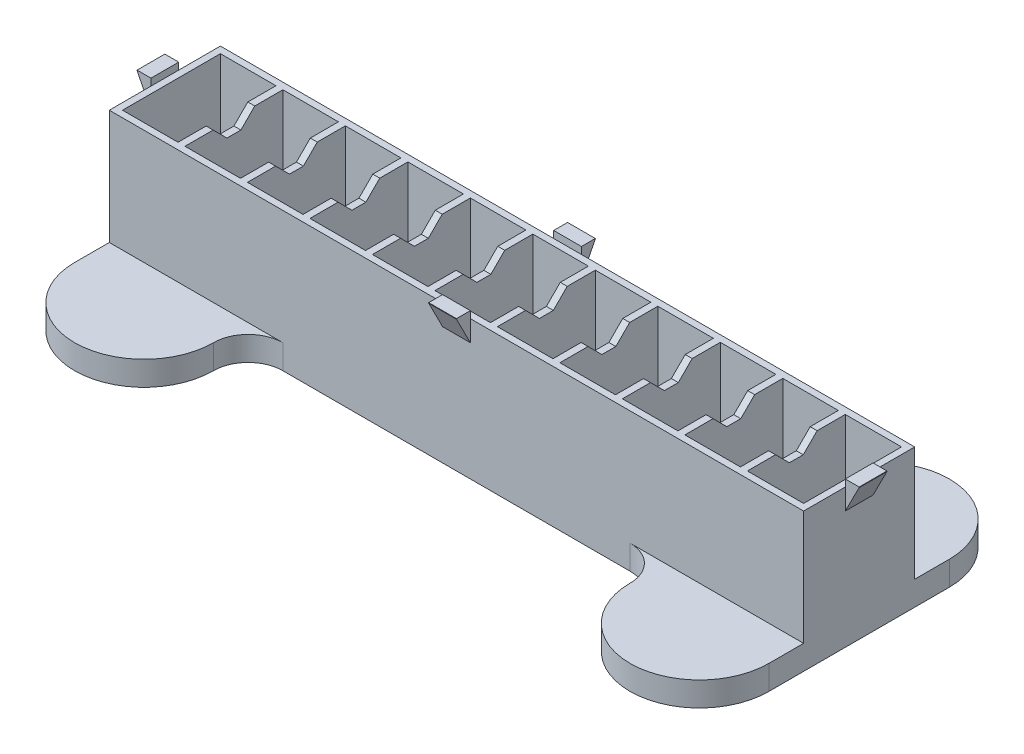
SolidWorks part; units mm, degrees
ref_plane "Front Plane" through (0, 0, 0) normal (0, 0, 1) x (1, 0, 0)
ref_plane "Top Plane" through (0, 0, 0) normal (0, 1, 0) x (1, 0, 0)
ref_plane "Right Plane" through (0, 0, 0) normal (1, 0, 0) x (0, 0, -1)
sketch "Sketch1" plane through (0, 0, 0) normal (0, 1, 0) x (1, 0, 0)
  line L1 (-275.0588, 111.5294) -> (-175.0588, 111.5294)
  line L2 (-275.0588, 111.5294) -> (-275.0588, 95.5294)
  line L3 (-275.0588, 95.5294) -> (-175.0588, 95.5294)
  line L4 (-175.0588, 111.5294) -> (-175.0588, 95.5294)
  dimension "D1" = 16
  dimension "D2" = 100
extrude "Boss-Extrude1" add sketch "Sketch1" along normal blind 20
sketch "Sketch2" plane through (-275.0588, 0, 0) normal (-1, 0, 0) x (0, 0, 1)
  line L0 (-111.5294, 20) -> (-95.5294, 20) construction
  line L1 (-110.5794, 20) -> (-96.4794, 20)
  line L2 (-110.5794, 20) -> (-110.5794, 8)
  line L4 (-96.4794, 20) -> (-96.4794, 8)
  line L5 (-111.5294, 20) -> (-111.5294, 0) construction
  arc A0 (-110.5794, 8) -> (-96.4794, 8) centre (-103.5294, 8) ccw
  point P8 (-103.5294, 20)
  point P9 (-103.5294, 20)
  dimension "D1" = 12
  dimension "D3" = 0.95
extrude "Cut-Extrude2" cut sketch "Sketch2" against normal blind 100
sketch "Sketch3" plane through (0, 20, 0) normal (0, 1, 0) x (1, 0, 0)
  line L0 (-225.0588, 111.5294) -> (-225.0588, 95.5294) construction
  line L1 (-175.0588, 111.5294) -> (-275.0588, 111.5294) construction
  line L2 (-275.0588, 95.5294) -> (-175.0588, 95.5294) construction
  line L3 (-175.0588, 95.5294) -> (-176.0088, 95.5294)
  line L4 (-275.0588, 111.5294) -> (-274.1088, 111.5294)
  line L5 (-275.0588, 111.5294) -> (-275.0588, 95.5294)
  line L6 (-275.0588, 95.5294) -> (-274.1088, 95.5294)
  line L7 (-274.1088, 111.5294) -> (-274.1088, 95.5294)
  line L8 (-175.0588, 111.5294) -> (-176.0088, 111.5294)
  line L9 (-176.0088, 111.5294) -> (-176.0088, 95.5294)
  line L10 (-175.0588, 111.5294) -> (-175.0588, 95.5294)
  dimension "D1" = 0.95
extrude "Boss-Extrude2" add sketch "Sketch3" against normal blind 20
sketch3d "3DSketch1" plane through (0, 0, 0) normal (0, 0, 1) x (1, 0, 0)
  dimension "D1" = 50
sketch "Sketch4" plane through (0, 20, 0) normal (0, 1, 0) x (1, 0, 0)
  line L0 (-274.1088, 103.5294) -> (-176.0088, 103.5294) construction
  line L1 (-274.1088, 96.4794) -> (-274.1088, 110.5794) construction
  line L2 (-176.0088, 110.5794) -> (-176.0088, 96.4794) construction
  line L3 (-176.0088, 110.5794) -> (-274.1088, 110.5794) construction
  line L4 (-266.1088, 110.5794) -> (-265.1088, 110.5794)
  line L5 (-266.1088, 110.5794) -> (-266.1088, 96.4794)
  line L6 (-266.1088, 96.4794) -> (-265.1088, 96.4794)
  line L7 (-265.1088, 110.5794) -> (-265.1088, 96.4794)
  line L8 (-176.0088, 96.4794) -> (-274.1088, 96.4794) construction
  line L9 (-265.1088, 103.5294) -> (-167.0088, 103.5294) construction
  line L10 (-257.1088, 110.5794) -> (-257.1088, 96.4794)
  line L11 (-256.1088, 110.5794) -> (-256.1088, 96.4794)
  line L12 (-257.1088, 96.4794) -> (-256.1088, 96.4794)
  line L13 (-257.1088, 110.5794) -> (-256.1088, 110.5794)
  line L14 (-256.1088, 103.5294) -> (-158.0088, 103.5294) construction
  line L15 (-248.1088, 110.5794) -> (-248.1088, 96.4794)
  line L16 (-247.1088, 110.5794) -> (-247.1088, 96.4794)
  line L17 (-248.1088, 96.4794) -> (-247.1088, 96.4794)
  line L18 (-248.1088, 110.5794) -> (-247.1088, 110.5794)
  line L19 (-247.1088, 103.5294) -> (-149.0088, 103.5294) construction
  line L20 (-239.1088, 110.5794) -> (-239.1088, 96.4794)
  line L21 (-238.1088, 110.5794) -> (-238.1088, 96.4794)
  line L22 (-239.1088, 96.4794) -> (-238.1088, 96.4794)
  line L23 (-239.1088, 110.5794) -> (-238.1088, 110.5794)
  line L24 (-238.1088, 103.5294) -> (-140.0088, 103.5294) construction
  line L25 (-230.1088, 110.5794) -> (-230.1088, 96.4794)
  line L26 (-229.1088, 110.5794) -> (-229.1088, 96.4794)
  line L27 (-230.1088, 96.4794) -> (-229.1088, 96.4794)
  line L28 (-230.1088, 110.5794) -> (-229.1088, 110.5794)
  line L29 (-229.1088, 103.5294) -> (-131.0088, 103.5294) construction
  line L30 (-221.1088, 110.5794) -> (-221.1088, 96.4794)
  line L31 (-220.1088, 110.5794) -> (-220.1088, 96.4794)
  line L32 (-221.1088, 96.4794) -> (-220.1088, 96.4794)
  line L33 (-221.1088, 110.5794) -> (-220.1088, 110.5794)
  line L34 (-220.1088, 103.5294) -> (-122.0088, 103.5294) construction
  line L35 (-212.1088, 110.5794) -> (-212.1088, 96.4794)
  line L36 (-211.1088, 110.5794) -> (-211.1088, 96.4794)
  line L37 (-212.1088, 96.4794) -> (-211.1088, 96.4794)
  line L38 (-212.1088, 110.5794) -> (-211.1088, 110.5794)
  line L39 (-211.1088, 103.5294) -> (-113.0088, 103.5294) construction
  line L40 (-203.1088, 110.5794) -> (-203.1088, 96.4794)
  line L41 (-202.1088, 110.5794) -> (-202.1088, 96.4794)
  line L42 (-203.1088, 96.4794) -> (-202.1088, 96.4794)
  line L43 (-203.1088, 110.5794) -> (-202.1088, 110.5794)
  line L44 (-202.1088, 103.5294) -> (-104.0088, 103.5294) construction
  line L45 (-194.1088, 110.5794) -> (-194.1088, 96.4794)
  line L46 (-193.1088, 110.5794) -> (-193.1088, 96.4794)
  line L47 (-194.1088, 96.4794) -> (-193.1088, 96.4794)
  line L48 (-194.1088, 110.5794) -> (-193.1088, 110.5794)
  line L49 (-193.1088, 103.5294) -> (-95.0088, 103.5294) construction
  line L50 (-185.1088, 110.5794) -> (-185.1088, 96.4794)
  line L51 (-184.1088, 110.5794) -> (-184.1088, 96.4794)
  line L52 (-185.1088, 96.4794) -> (-184.1088, 96.4794)
  line L53 (-185.1088, 110.5794) -> (-184.1088, 110.5794)
  line L54 (-176.0088, 110.5794) -> (-176.0088, 96.4794) construction
  dimension "D1" = 8
  dimension "D2" = 9
  dimension "D4" = 8.1
  dimension "D3" = 10
extrude "Boss-Extrude3" add sketch "Sketch4" against normal blind 20
sketch "Sketch5" plane through (0, 20, 0) normal (0, 1, 0) x (1, 0, 0)
  line L0 (-274.1088, 103.5294) -> (-176.0088, 103.5294) construction
  line L1 (-274.1088, 96.4794) -> (-274.1088, 110.5794) construction
  line L2 (-176.0088, 110.5794) -> (-176.0088, 96.4794) construction
  line L4 (-272.5588, 102.5294) -> (-177.5588, 102.5294)
  line L5 (-272.5588, 102.5294) -> (-272.5588, 104.5294)
  line L6 (-272.5588, 104.5294) -> (-177.5588, 104.5294)
  line L7 (-177.5588, 102.5294) -> (-177.5588, 104.5294)
  line L8 (-272.5588, 102.5294) -> (-177.5588, 104.5294) construction
  line L9 (-272.5588, 104.5294) -> (-177.5588, 102.5294) construction
  point P6 (-225.0588, 103.5294)
  dimension "D1" = 2
  dimension "D2" = 95
extrude "Cut-Extrude3" cut sketch "Sketch5" against normal blind 2
sketch "Sketch6" plane through (0, 0, 0) normal (0, -1, 0) x (1, 0, 0)
  line L0 (-225.0588, -95.5294) -> (-225.0588, -111.5294) construction
  line L1 (-275.0588, -95.5294) -> (-175.0588, -95.5294) construction
  line L2 (-175.0588, -111.5294) -> (-275.0588, -111.5294) construction
  line L3 (-275.0588, -103.5294) -> (-175.0588, -103.5294) construction
  line L4 (-275.0588, -111.5294) -> (-275.0588, -95.5294) construction
  line L5 (-175.0588, -95.5294) -> (-175.0588, -111.5294) construction
  line L6 (-275.0588, -90.5294) -> (-275.0588, -95.5294)
  line L9 (-255.0588, -90.5294) -> (-255.0588, -95.5294)
  line L11 (-175.0588, -111.5294) -> (-175.0588, -116.5294)
  line L12 (-195.0588, -90.5294) -> (-195.0588, -95.5294)
  line L13 (-175.0588, -90.5294) -> (-175.0588, -95.5294)
  line L14 (-275.0588, -95.5294) -> (-255.0588, -95.5294)
  line L15 (-275.0588, -111.5294) -> (-255.0588, -111.5294)
  line L16 (-195.0588, -111.5294) -> (-175.0588, -111.5294)
  line L17 (-175.0588, -95.5294) -> (-195.0588, -95.5294)
  line L18 (-255.0588, -111.5294) -> (-255.0588, -116.5294)
  line L19 (-275.0588, -111.5294) -> (-275.0588, -116.5294)
  line L20 (-195.0588, -111.5294) -> (-195.0588, -116.5294)
  arc A0 (-255.0588, -90.5294) -> (-275.0588, -90.5294) centre (-265.0588, -90.5294) ccw
  arc A1 (-255.0588, -116.5294) -> (-275.0588, -116.5294) centre (-265.0588, -116.5294) cw
  arc A2 (-195.0588, -116.5294) -> (-175.0588, -116.5294) centre (-185.0588, -116.5294) ccw
  arc A3 (-195.0588, -90.5294) -> (-175.0588, -90.5294) centre (-185.0588, -90.5294) cw
  dimension "D3" = 20
  dimension "D2" = 5
extrude "Boss-Extrude4" add sketch "Sketch6" against normal blind 3.5
fillet "Fillet1" radius 5 4 edges at (-195.0588, 1.75, -95.5294) (-255.0588, 1.75, -95.5294) (-255.0588, 1.75, -111.5294) (-195.0588, 1.75, -111.5294)
sketch "Sketch7" plane through (0, 20, 0) normal (0, 1, 0) x (1, 0, 0)
  line L0 (-275.0588, 95.5294) -> (-175.0588, 95.5294)
  line L1 (-275.0588, 95.5294) -> (-275.0588, 111.5294)
  line L2 (-175.0588, 95.5294) -> (-175.0588, 111.5294)
  line L3 (-275.0588, 111.5294) -> (-175.0588, 111.5294)
  line L4 (-175.0588, 111.5294) -> (-275.0588, 111.5294) construction
  line L5 (-274.1088, 96.4794) -> (-176.0088, 96.4794)
  line L6 (-176.0088, 96.4794) -> (-176.0088, 110.5794)
  line L7 (-274.1088, 110.5794) -> (-176.0088, 110.5794)
  line L8 (-274.1088, 96.4794) -> (-274.1088, 110.5794)
  dimension "D1" = 0.95
fillet "Fillet2" radius 2 20 edges at (-238.6088, 20, -102.5294) (-238.6088, 20, -104.5294) (-202.6088, 20, -102.5294) (-202.6088, 20, -104.5294) (-184.6088, 20, -102.5294) (-184.6088, 20, -104.5294) (-193.6088, 20, -102.5294) (-193.6088, 20, -104.5294) (-211.6088, 20, -104.5294) (-211.6088, 20, -102.5294) (-220.6088, 20, -102.5294) (-220.6088, 20, -104.5294) (-229.6088, 20, -102.5294) (-229.6088, 20, -104.5294) (-247.6088, 20, -104.5294) (-247.6088, 20, -102.5294) (-256.6088, 20, -104.5294) (-256.6088, 20, -102.5294) (-265.6088, 20, -104.5294) (-265.6088, 20, -102.5294) profile chamfer
sketch "Sketch8" plane through (0, 0, -111.5294) normal (0, 0, -1) x (-1, 0, 0)
  line L0 (175.0588, 17) -> (275.0588, 17) construction
  line L1 (175.0588, 20) -> (175.0588, 3.5) construction
  line L2 (275.0588, 20) -> (275.0588, 3.5) construction
  line L3 (275.0588, 20) -> (175.0588, 20) construction
  dimension "D1" = 3
ref_plane "Plane1" through (0, 17, 0) normal (0, 1, 0) x (-1, 0, 0)
sketch "Sketch9" plane through (0, 17, 0) normal (0, 1, 0) x (-1, 0, 0)
  line L0 (175.0588, -95.5294) -> (175.0588, -111.5294) construction
  line L1 (175.0588, -105.5294) -> (173.0588, -105.5294)
  line L2 (175.0588, -105.5294) -> (175.0588, -101.5294)
  line L3 (175.0588, -101.5294) -> (173.0588, -101.5294)
  line L4 (173.0588, -105.5294) -> (173.0588, -101.5294)
  line L5 (225.0588, -110.5794) -> (225.0588, -96.4794) construction
  line L6 (274.1088, -110.5794) -> (176.0088, -110.5794) construction
  line L7 (274.1088, -96.4794) -> (176.0088, -96.4794) construction
  line L8 (275.0588, -101.5294) -> (277.0588, -101.5294)
  line L9 (277.0588, -105.5294) -> (277.0588, -101.5294)
  line L10 (275.0588, -105.5294) -> (277.0588, -105.5294)
  line L11 (275.0588, -105.5294) -> (275.0588, -101.5294)
  line L12 (275.0588, -111.5294) -> (175.0588, -111.5294) construction
  line L13 (223.0588, -111.5294) -> (227.0588, -111.5294)
  line L14 (223.0588, -111.5294) -> (223.0588, -113.5294)
  line L15 (223.0588, -113.5294) -> (227.0588, -113.5294)
  line L16 (227.0588, -111.5294) -> (227.0588, -113.5294)
  line L17 (225.0588, -103.5294) -> (213.4013, -103.5294) construction
  line L18 (223.0588, -93.5294) -> (227.0588, -93.5294)
  line L19 (227.0588, -95.5294) -> (227.0588, -93.5294)
  line L20 (223.0588, -95.5294) -> (227.0588, -95.5294)
  line L21 (223.0588, -95.5294) -> (223.0588, -93.5294)
  point P6 (175.0588, -103.5294)
  point P7 (175.0588, -103.5294)
  point P24 (225.0588, -111.5294)
  point P25 (225.0588, -111.5294)
  dimension "D1" = 2
  dimension "D2" = 4
  dimension "D3" = 4
  dimension "D4" = 2
extrude "Boss-Extrude5" add sketch "Sketch9" along normal blind 4
chamfer "Chamfer1" distance 2 angle 63 4 edges at (-225.0588, 17, -113.5294) (-173.0588, 17, -103.5294) (-225.0588, 17, -93.5294) (-277.0588, 17, -103.5294) first distance on face at (-225.0588, 17, -112.5294) first distance on face at (-174.0588, 17, -103.5294) first distance on face at (-225.0588, 17, -94.5294) first distance on face at (-276.0588, 17, -103.5294)
